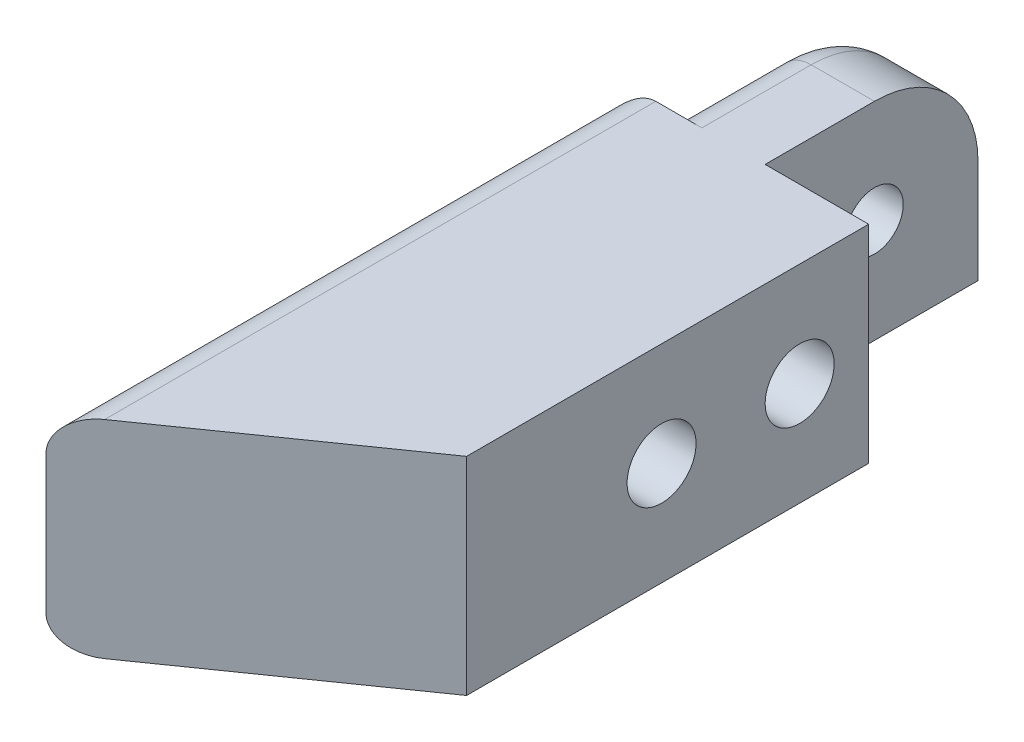
SolidWorks part; units mm, degrees
ref_plane "Front Plane" through (0, 0, 0) normal (0, 0, 1) x (1, 0, 0)
ref_plane "Top Plane" through (0, 0, 0) normal (0, 1, 0) x (1, 0, 0)
ref_plane "Right Plane" through (0, 0, 0) normal (1, 0, 0) x (0, 0, -1)
sketch "Sketch1" plane through (0, 0, 0) normal (0, 1, 0) x (1, 0, 0)
  line L0 (-8.25, 17.4728) -> (-8.25, -32.5272)
  line L1 (-8.25, -32.5272) -> (13.25, -17.4728)
  line L2 (13.25, -17.4728) -> (13.25, 17.4728)
  line L3 (13.25, 17.4728) -> (4.25, 17.4728)
  line L4 (4.25, 17.4728) -> (4.25, 35.9728)
  line L5 (4.25, 35.9728) -> (-4.25, 35.9728)
  line L6 (-4.25, 35.9728) -> (-4.25, 17.4728)
  line L7 (-4.25, 17.4728) -> (-8.25, 17.4728)
  line L8 (-8.25, 0) -> (13.25, 0) construction
  line L9 (0, 35.9728) -> (0, -26.7505) construction
  dimension "D1" = 9
  dimension "D2" = 4
  dimension "D3" = 8.5
  dimension "D4" = 18.5
  dimension "D5" = 50
  dimension "D6" = 55
extrude "Boss-Extrude1" add sketch "Sketch1" along normal blind 18
sketch "Sketch3" plane through (-8.25, 0, 0) normal (-1, 0, 0) x (0, 0, 1)
  line L0 (-26.9728, 18) -> (-26.9728, 0) construction
  line L1 (-35.9728, 9) -> (-35.9728, 18)
  line L2 (-35.9728, 18) -> (-26.9728, 18)
  line L3 (-35.9728, 18) -> (-17.4728, 18) construction
  line L5 (-35.9728, 18) -> (-35.9728, 0) construction
  line L6 (-35.9728, 9) -> (32.5272, 9) construction
  line L7 (32.5272, 18) -> (32.5272, 0) construction
  line L8 (-17.4728, 18) -> (-17.4728, 0) construction
  arc A0 (-26.9728, 18) -> (-35.9728, 9) centre (-26.9728, 9) ccw
  circle A1 centre (-26.9728, 9) radius 2.5
  circle A2 centre (-11.4728, 9) radius 3
  circle A3 centre (0.5272, 9) radius 3
  point P2 (-26.9728, 9)
  point P13 (-11.4728, 9)
  point P14 (0.5272, 9)
  dimension "D4" = 6
  dimension "D5" = 5
  dimension "D1" = 9
  dimension "D2" = 6
  dimension "D3" = 12
extrude "Cut-Extrude1" cut sketch "Sketch3" against normal through all
fillet "Fillet1" radius 3 3 edges at (-4.25, 18, -22.2228) (-4.25, 15.364, -33.3367) (-4.25, 4.5, -35.9728)
fillet "Fillet2" radius 3 3 edges at (-8.25, 9, -17.4728) (-8.25, 0, 7.5272) (-8.25, 18, 7.5272)
